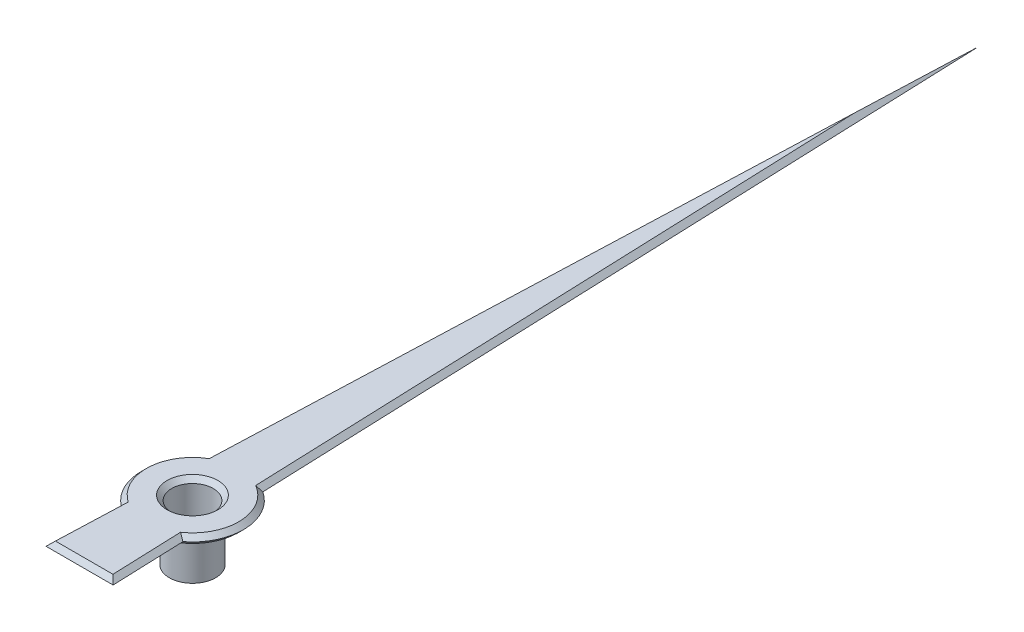
SolidWorks part; units mm, degrees
ref_plane "Front Plane" through (0, 0, 0) normal (0, 0, 1) x (1, 0, 0)
ref_plane "Top Plane" through (0, 0, 0) normal (0, 1, 0) x (1, 0, 0)
ref_plane "Right Plane" through (0, 0, 0) normal (1, 0, 0) x (0, 0, -1)
sketch "Sketch1" plane through (0, 0, 0) normal (0, 1, 0) x (1, 0, 0)
  circle A0 centre (0, 0) radius 0.5
  dimension "D1" = 1
extrude "Boss-Extrude1" add sketch "Sketch1" against normal blind 1 and the other way blind 0.1
sketch "Sketch2" plane through (0, 0.1, 0) normal (0, 1, 0) x (1, 0, 0)
  circle A0 centre (0, 0) radius 1.1
  dimension "D1" = 2.2
extrude "Boss-Extrude2" add sketch "Sketch2" along normal blind 0.2
sketch "Sketch3" plane through (0, 0.3, 0) normal (0, 1, 0) x (1, 0, 0)
  line L1 (0, 17) -> (-0.7264, -2.4438)
  line L2 (-0.7264, -2.4438) -> (0.7264, -2.4438)
  line L3 (0, 17) -> (0.7264, -2.4438)
extrude "Boss-Extrude3" add sketch "Sketch3" against normal blind 0.2
sketch "Sketch4" plane through (0, 0.3, 0) normal (0, 1, 0) x (1, 0, 0)
  circle A0 centre (0, 0) radius 0.45
  dimension "D1" = 0.9
extrude "Cut-Extrude1" cut sketch "Sketch4" against normal blind 1
chamfer "Chamfer1" distance 0.1 angle 45 16 edges at (0, 0.1, 0.5) (-0.6971, 0.1, 1.659) (0, 0.1, 2.4438) (0.6971, 0.1, 1.659) (1.0992, 0.1, -0.0411) (0.3003, 0.1, -8.9608) (-0.3003, 0.1, -8.9608) (-1.0992, 0.1, -0.0411) (-0.3003, 0.3, -8.9608) (0.3003, 0.3, -8.9608) (1.0992, 0.3, -0.0411) (0.6971, 0.3, 1.659) (0, 0.3, 2.4438) (-0.6971, 0.3, 1.659) (-1.0992, 0.3, -0.0411) (0, 0.3, 0.45)
